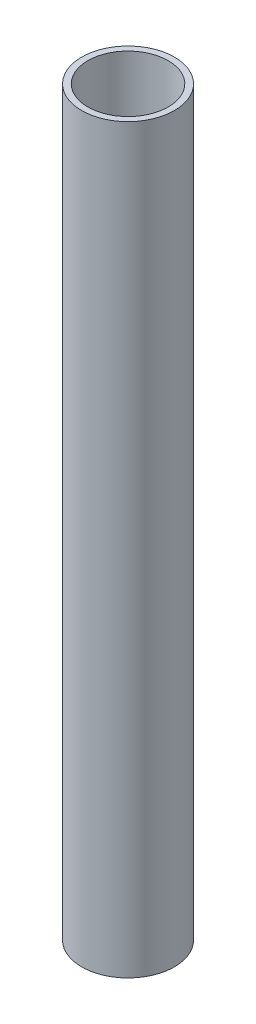
SolidWorks part; units mm, degrees
ref_plane "Front Plane" through (0, 0, 0) normal (0, 0, 1) x (1, 0, 0)
ref_plane "Top Plane" through (0, 0, 0) normal (0, 1, 0) x (1, 0, 0)
ref_plane "Right Plane" through (0, 0, 0) normal (1, 0, 0) x (0, 0, -1)
sketch "Sketch1" plane through (0, 0, 0) normal (0, 1, 0) x (1, 0, 0)
  circle A0 centre (0, 0) radius 9.525
  circle A1 centre (0, 0) radius 8.255
  dimension "D1" = 19.05
  dimension "D2" = 1.27
extrude "Boss-Extrude1" add sketch "Sketch1" along normal blind 152.4
